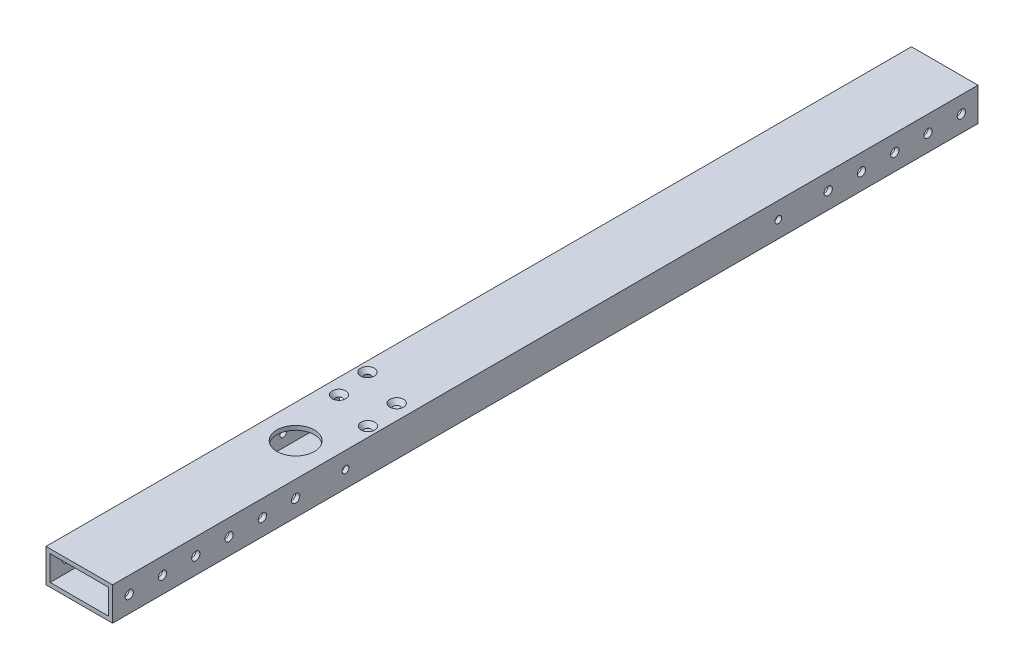
SolidWorks part; units mm, degrees
material "6061 Alloy"
ref_plane "Front Plane" through (0, 0, 0) normal (0, 0, 1) x (1, 0, 0)
ref_plane "Top Plane" through (0, 0, 0) normal (0, 1, 0) x (1, 0, 0)
ref_plane "Right Plane" through (0, 0, 0) normal (1, 0, 0) x (0, 0, -1)
sketch "Sketch1" plane through (0, 0, 0) normal (0, 0, 1) x (1, 0, 0)
  line L0 (-22.225, 9.525) -> (22.225, 9.525)
  line L2 (-25.4, 12.7) -> (25.4, 12.7)
  line L3 (-25.4, 12.7) -> (-25.4, -12.7)
  line L4 (-25.4, -12.7) -> (25.4, -12.7)
  line L5 (25.4, 12.7) -> (25.4, -12.7)
  line L10 (22.225, 9.525) -> (22.225, -9.525)
  line L11 (-22.225, -9.525) -> (22.225, -9.525)
  line L12 (-22.225, 9.525) -> (-22.225, -9.525)
  point P12 (0, 12.7)
  point P14 (25.4, 0)
  dimension "Wall Thickness" = 3.175
  dimension "Outside Width" = 50.8
  dimension "Outside Height" = 25.4
  dimension "Inside Height" = 19.05
  dimension "Inside Width" = 44.45
sketch "Sketch2" plane through (0, 0, 0) normal (1, 0, 0) x (0, 0, -1)
  line L0 (330.2, 0) -> (-330.2, 0)
  point P4 (0, 0)
  point P7 (-330.2, 0)
  point P10 (330.2, 0)
  dimension "Length" = 660.4
sketch "Sketch3" plane through (0, 0, 0) normal (0, 0, 1) x (1, 0, 0)
  line L21 (25.4, 12.7) -> (-25.4, 12.7)
  line L22 (25.4, -12.7) -> (25.4, 12.7)
  line L23 (-25.4, -12.7) -> (25.4, -12.7)
  line L24 (-25.4, 12.7) -> (-25.4, -12.7)
  line L25 (25.4, 12.7) -> (-25.4, 12.7)
  line L26 (25.4, -12.7) -> (25.4, 12.7)
  line L27 (-25.4, -12.7) -> (25.4, -12.7)
  line L28 (-25.4, 12.7) -> (-25.4, -12.7)
  line L29 (22.225, 9.525) -> (-22.225, 9.525)
  line L30 (22.225, -9.525) -> (22.225, 9.525)
  line L31 (-22.225, -9.525) -> (22.225, -9.525)
  line L32 (-22.225, 9.525) -> (-22.225, -9.525)
  line L33 (22.225, 9.525) -> (-22.225, 9.525)
  line L34 (22.225, -9.525) -> (22.225, 9.525)
  line L35 (-22.225, -9.525) -> (22.225, -9.525)
  line L36 (-22.225, 9.525) -> (-22.225, -9.525)
  dimension "D1" = 0
  dimension "D2" = 0
extrude "Boss-Extrude1" add sketch "Sketch3" along normal up to vertex (330.2 mm away) and the other way up to vertex (330.2 mm away) up to point (0, 0, 330.2) other way up to point (0, 0, -330.2)
sketch "Drawing Reference" plane through (0, 0, 0) normal (1, 0, 0) x (0, 0, -1)
  line L0 (-330.2, 0) -> (330.2, 0) construction
  line L1 (0, -12.7) -> (0, 12.7) construction
  line L2 (-330.2, -12.7) -> (330.2, -12.7) construction
  line L5 (-330.2, 12.7) -> (330.2, 12.7) construction
  point P7 (-293.624, 0)
  point P8 (293.624, 0)
  dimension "D1" = 36.576
sketch "Sketch5" plane through (25.4, 0, 0) normal (1, 0, 0) x (0, 0, -1)
  line L2 (-266.7, 0) -> (-241.3, 0)
  line L3 (-241.3, 0) -> (-215.9, 0)
  line L4 (-215.9, 0) -> (-190.5, 0)
  line L5 (-317.5, 0) -> (-330.2, 0)
  line L6 (-330.2, -12.7) -> (-330.2, 12.7) construction
  line L7 (-317.5, 0) -> (-292.1, 0)
  line L8 (-292.1, 0) -> (-266.7, 0)
sketch "Sketch8" plane through (25.4, 0, 0) normal (1, 0, 0) x (0, 0, -1)
  line L0 (330.2, 0) -> (292.1, 0)
  line L1 (330.2, -12.7) -> (330.2, 12.7) construction
  line L2 (292.1, 0) -> (266.7, 0)
  line L3 (266.7, 0) -> (241.3, 0)
  line L4 (241.3, 0) -> (215.9, 0)
  line L5 (330.2, 0) -> (317.5, 0)
hole_wizard "1/4 (0.25) Diameter Hole3" positions "Sketch12" profile "Sketch13" hole size "1/4" standard "ANSI Inch" end condition through all
sketch "Sketch12" plane through (-25.4, 0, 0) normal (-1, 0, 0) x (0, 0, 1)
  point P4 (-317.5, 0)
sketch "Sketch13" plane through (-25.4, 0, -317.5) normal (0, 1, 0) x (0, 0, 1)
  line L0 (0, 0) -> (0, 50.8)
  line L1 (0, 50.8) -> (3.175, 50.8)
  line L2 (3.175, 50.8) -> (3.175, 0)
  line L5 (3.175, 0) -> (0, 0)
  line L11 (0, -6.35) -> (0, 107.95) construction
  dimension "Thru Hole Dia." = 6.35
  dimension "Thru Hole Depth" = 50.8
hole_wizard "1/4 (0.25) Diameter Hole4" positions "Sketch14" profile "Sketch15" hole size "1/4" standard "ANSI Inch" end condition through all
sketch "Sketch14" plane through (-25.4, 0, 0) normal (-1, 0, 0) x (0, 0, 1)
  point P0 (292.1, 0)
  point P3 (317.5, 0)
sketch "Sketch15" plane through (-25.4, 0, 292.1) normal (0, 1, 0) x (0, 0, 1)
  line L0 (0, 0) -> (0, 50.8)
  line L1 (0, 50.8) -> (3.175, 50.8)
  line L2 (3.175, 50.8) -> (3.175, 0)
  line L5 (3.175, 0) -> (0, 0)
  line L11 (0, -6.35) -> (0, 107.95) construction
  dimension "Thru Hole Dia." = 6.35
  dimension "Thru Hole Depth" = 50.8
hole_wizard "1/4 (0.25) Diameter Hole5" positions "Sketch17" profile "Sketch18" hole size "1/4" standard "ANSI Inch" end condition through all
sketch "Sketch17" plane through (25.4, 0, 0) normal (1, 0, 0) x (0, 0, -1)
  point P0 (292.1, 0)
  point P3 (266.7, 0)
sketch "Sketch18" plane through (25.4, 0, -292.1) normal (0, 1, 0) x (0, 0, -1)
  line L0 (0, 0) -> (0, 50.8)
  line L1 (0, 50.8) -> (3.175, 50.8)
  line L2 (3.175, 50.8) -> (3.175, 0)
  line L5 (3.175, 0) -> (0, 0)
  line L11 (0, -6.35) -> (0, 107.95) construction
  dimension "Thru Hole Dia." = 6.35
  dimension "Thru Hole Depth" = 50.8
hole_wizard "1/4 (0.25) Diameter Hole6" positions "Sketch19" profile "Sketch20" hole size "1/4" standard "ANSI Inch" end condition through all
sketch "Sketch19" plane through (25.4, 0, 0) normal (1, 0, 0) x (0, 0, -1)
  point P0 (215.9, 0)
  point P3 (241.3, 0)
sketch "Sketch20" plane through (25.4, 0, -215.9) normal (0, 1, 0) x (0, 0, -1)
  line L0 (0, 0) -> (0, 50.8)
  line L1 (0, 50.8) -> (3.175, 50.8)
  line L2 (3.175, 50.8) -> (3.175, 0)
  line L5 (3.175, 0) -> (0, 0)
  line L11 (0, -6.35) -> (0, 107.95) construction
  dimension "Thru Hole Dia." = 6.35
  dimension "Thru Hole Depth" = 50.8
hole_wizard "1/4 (0.25) Diameter Hole7" positions "Sketch21" profile "Sketch22" hole size "1/4" standard "ANSI Inch" end condition through all
sketch "Sketch21" plane through (25.4, 0, 0) normal (1, 0, 0) x (0, 0, -1)
  point P0 (-190.5, 0)
  point P3 (-215.9, 0)
sketch "Sketch22" plane through (25.4, 0, 190.5) normal (0, 1, 0) x (0, 0, -1)
  line L0 (0, 0) -> (0, 50.8)
  line L1 (0, 50.8) -> (3.175, 50.8)
  line L2 (3.175, 50.8) -> (3.175, 0)
  line L5 (3.175, 0) -> (0, 0)
  line L11 (0, -6.35) -> (0, 107.95) construction
  dimension "Thru Hole Dia." = 6.35
  dimension "Thru Hole Depth" = 50.8
hole_wizard "1/4 (0.25) Diameter Hole8" positions "Sketch23" profile "Sketch24" hole size "1/4" standard "ANSI Inch" end condition through all
sketch "Sketch23" plane through (25.4, 0, 0) normal (1, 0, 0) x (0, 0, -1)
  point P0 (-266.7, 0)
  point P3 (-241.3, 0)
sketch "Sketch24" plane through (25.4, 0, 266.7) normal (0, 1, 0) x (0, 0, -1)
  line L0 (0, 0) -> (0, 50.8)
  line L1 (0, 50.8) -> (3.175, 50.8)
  line L2 (3.175, 50.8) -> (3.175, 0)
  line L5 (3.175, 0) -> (0, 0)
  line L11 (0, -6.35) -> (0, 107.95) construction
  dimension "Thru Hole Dia." = 6.35
  dimension "Thru Hole Depth" = 50.8
sketch "Sketch25" plane through (25.4, 0, 0) normal (1, 0, 0) x (0, 0, -1)
  line L0 (-190.5, 0) -> (-152.4, 0)
  line L1 (215.9, 0) -> (177.8, 0)
hole_wizard "13/64 (0.20313) Diameter Hole1" positions "Sketch26" profile "Sketch27" hole size "13/64" standard "ANSI Inch" end condition through all
sketch "Sketch26" plane through (25.4, 0, 0) normal (1, 0, 0) x (0, 0, -1)
  point P0 (-152.4, 0)
  point P3 (177.8, 0)
sketch "Sketch27" plane through (25.4, 0, 152.4) normal (0, 1, 0) x (0, 0, -1)
  line L0 (0, 0) -> (0, 50.8)
  line L1 (0, 50.8) -> (2.5798, 50.8)
  line L2 (2.5798, 50.8) -> (2.5798, 0)
  line L5 (2.5798, 0) -> (0, 0)
  line L11 (0, -6.35) -> (0, 107.95) construction
  dimension "Thru Hole Dia." = 5.1595
  dimension "Thru Hole Depth" = 50.8
sketch "Sketch30" plane through (-25.4, 0, 0) normal (-1, 0, 0) x (0, 0, 1)
  point P0 (-128.5875, 0)
  point P1 (-103.1875, 0)
  point P2 (77.7875, 0)
  point P3 (103.1875, 0)
hole_wizard "1/2 (0.5) Diameter Hole1" positions "Sketch33" profile "Sketch34" hole size "1/2" standard "ANSI Inch"
sketch "Sketch33" plane through (-25.4, 0, 0) normal (-1, 0, 0) x (0, 0, 1)
  point P0 (-128.5875, 0)
  point P3 (-103.1875, 0)
  point P7 (77.7875, 0)
  point P10 (103.1875, 0)
sketch "Sketch34" plane through (-25.4, 0, -128.5875) normal (0, 1, 0) x (0, 0, 1)
  line L0 (0, 0) -> (0, 10.1655)
  line L1 (0, 10.1655) -> (6.35, 6.35)
  line L2 (6.35, 6.35) -> (6.35, 0)
  line L5 (6.35, 0) -> (0, 0)
  line L10 (0, 10.1655) -> (-6.35, 6.35) construction
  line L11 (0, -6.35) -> (0, 107.95) construction
  dimension "Hole Dia." = 12.7
  dimension "Hole Depth" = 6.35
  dimension "Drill Angle" = 118
sketch "Sketch36" plane through (0, -12.7, 0) normal (0, -1, 0) x (1, 0, 0)
  line L0 (-25.4, 165.1081) -> (25.4, 165.1081) construction
  line L1 (-25.4, 330.2) -> (-25.4, -330.2) construction
  line L2 (25.4, 330.2) -> (25.4, -330.2) construction
  line L3 (0, 165.1081) -> (7.7911, 138.8057) construction
  line L5 (7.7911, 138.8057) -> (-2.7276, 135.69) construction
  line L6 (-25.4, 128.9741) -> (575.1111, 306.8536) construction
  circle A0 centre (0, 165.1081) radius 14.2875
  dimension "D2" = 28.575
  dimension "D1" = 27.432
extrude "Cut-Extrude1" cut sketch "Sketch36" against normal through all
sketch "Sketch37" plane through (0, -12.7, 0) normal (0, -1, 0) x (1, 0, 0)
  line L1 (13.819, 101.7821) -> (17.931, 127.883) construction
  line L5 (-13.819, 118.2319) -> (17.931, 127.883) construction
  line L6 (-17.931, 92.3773) -> (13.819, 101.7821) construction
  line L7 (-13.819, 118.2319) -> (-17.931, 92.3773) construction
hole_wizard "#10 Clearance Hole4" positions "Sketch45" profile "Sketch46" hole size "#10" standard "ANSI Inch" end condition through all
sketch "Sketch45" plane through (0, -12.7, 0) normal (0, -1, 0) x (-1, 0, 0)
  point P0 (-13.819, -101.7821)
  point P3 (-17.931, -127.883)
  point P6 (13.819, -118.2319)
  point P9 (17.931, -92.3773)
sketch "Sketch46" plane through (13.819, -12.7, 101.7821) normal (1, 0, 0) x (0, 0, -1)
  line L0 (0, 0) -> (0, 25.4)
  line L1 (0, 25.4) -> (5.2197, 25.4)
  line L2 (2.4892, 22.2589) -> (2.4892, 0)
  line L5 (2.4892, 0) -> (0, 0)
  line L7 (5.2197, 25.4) -> (2.4892, 22.2589)
  line L8 (-5.2197, 25.4) -> (-2.4892, 22.2589) construction
  line L11 (0, -6.35) -> (0, 107.95) construction
  dimension "Thru Hole Dia." = 4.9784
  dimension "Thru Hole Depth" = 25.4
  dimension "Far C'Sink Dia." = 10.4394
  dimension "Far C'Sink Angle" = 82
equation "\"D1@Drawing Reference\"=\"Outside Width@Sketch1\" * 0.72"
